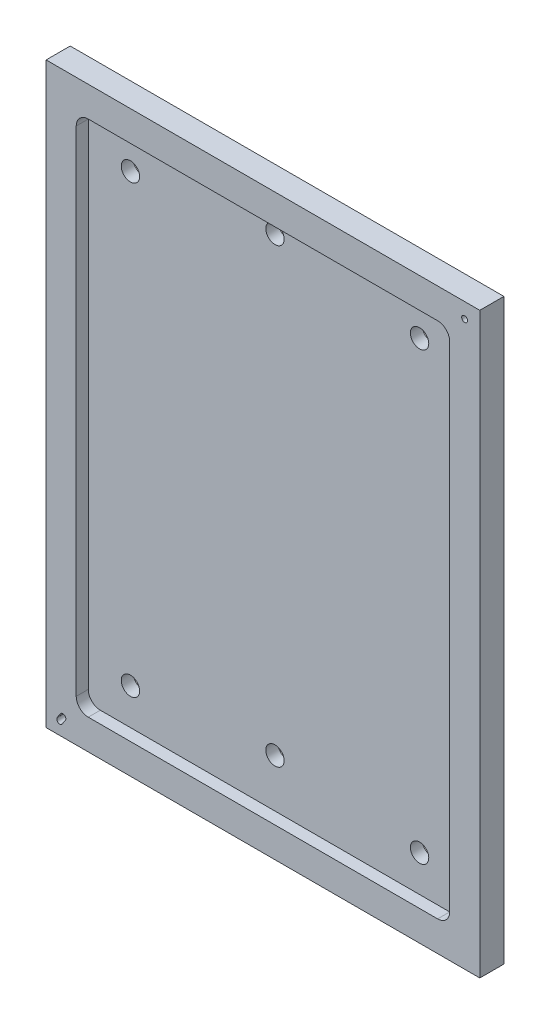
SolidWorks part; units mm, degrees
ref_plane "Front Plane" through (0, 0, 0) normal (0, 0, 1) x (1, 0, 0)
ref_plane "Top Plane" through (0, 0, 0) normal (0, 1, 0) x (1, 0, 0)
ref_plane "Right Plane" through (0, 0, 0) normal (1, 0, 0) x (0, 0, -1)
sketch "Sketch1" plane through (0, 0, 0) normal (0, 0, 1) x (1, 0, 0)
  line L1 (114.3, -152.4) -> (-114.3, -152.4)
  line L2 (114.3, -152.4) -> (114.3, 152.4)
  line L3 (114.3, 152.4) -> (-114.3, 152.4)
  line L4 (-114.3, -152.4) -> (-114.3, 152.4)
  line L5 (114.3, -152.4) -> (-114.3, 152.4) construction
  line L6 (114.3, 152.4) -> (-114.3, -152.4) construction
  point P0 (0, 0)
  dimension "D1" = 228.6
  dimension "D2" = 304.8
extrude "Boss-Extrude1" add sketch "Sketch1" along normal blind 12.7
sketch "Sketch2" plane through (0, 0, 12.7) normal (0, 0, 1) x (1, 0, 0)
  line L0 (-114.3, 152.4) -> (-114.3, -152.4) construction
  line L1 (92.075, -136.525) -> (-92.075, -136.525)
  line L2 (98.425, -130.175) -> (98.425, 130.175)
  line L3 (92.075, 136.525) -> (-92.075, 136.525)
  line L4 (-98.425, -130.175) -> (-98.425, 130.175)
  line L5 (98.425, -136.525) -> (-98.425, 136.525) construction
  line L6 (98.425, 136.525) -> (-98.425, -136.525) construction
  line L7 (114.3, 152.4) -> (-114.3, 152.4) construction
  arc A0 (-92.075, -136.525) -> (-98.425, -130.175) centre (-92.075, -130.175) cw
  arc A1 (92.075, -136.525) -> (98.425, -130.175) centre (92.075, -130.175) ccw
  arc A2 (98.425, 130.175) -> (92.075, 136.525) centre (92.075, 130.175) ccw
  arc A3 (-92.075, 136.525) -> (-98.425, 130.175) centre (-92.075, 130.175) ccw
  point P0 (0, 0)
  dimension "D3" = 6.35
  dimension "D1" = 15.875
  dimension "D2" = 15.875
extrude "Cut-Extrude1" cut sketch "Sketch2" against normal blind 6.35
sketch "Sketch4" plane through (0, 0, 6.35) normal (0, 0, 1) x (1, 0, 0)
  line L0 (114.3, 152.4) -> (-114.3, 152.4) construction
  line L4 (-114.3, 152.4) -> (-114.3, -152.4) construction
  line L5 (114.3, -152.4) -> (114.3, 152.4) construction
  line L6 (-114.3, -152.4) -> (114.3, -152.4) construction
  line L8 (-92.075, -136.525) -> (92.075, -136.525) construction
  circle A0 centre (-76.2, 117.4) radius 4.85
  circle A1 centre (76.2, 117.4) radius 4.85
  circle A2 centre (-76.2, -117.4) radius 4.85
  circle A3 centre (76.2, -117.4) radius 4.85
  circle A4 centre (0, 126.925) radius 4.85
  circle A5 centre (0, -111.125) radius 4.85
  dimension "D1" = 9.7
  dimension "D2" = 9.7
  dimension "D3" = 9.7
  dimension "D4" = 9.7
  dimension "D13" = 9.7
  dimension "D14" = 9.7
  dimension "D15" = 35
  dimension "D5" = 9.525
  dimension "D6" = 38.1
  dimension "D7" = 38.1
  dimension "D8" = 0
  dimension "D9" = 35
  dimension "D10" = 38.1
  dimension "D11" = 38.1
  dimension "D12" = 35
  dimension "D16" = 25.4
extrude "Cut-Extrude2" cut sketch "Sketch4" against normal through all
hole_wizard "Ø3.1 (3.1) Diameter Hole1" positions "Sketch5" profile "Sketch6" hole size "Ø3.1" standard "ANSI Metric"
sketch "Sketch5" plane through (0, 0, 12.7) normal (0, 0, 1) x (1, 0, 0)
  line L0 (114.3, 152.4) -> (-114.3, 152.4) construction
  line L1 (114.3, -152.4) -> (114.3, 152.4) construction
  point P0 (106.3, 144.4)
  dimension "D1" = 8
  dimension "D2" = 8
sketch "Sketch6" plane through (106.3, 144.4, 12.7) normal (1, 0, 0) x (0, -1, 0)
  line L0 (0, 0) -> (0, 5.9313)
  line L1 (0, 5.9313) -> (1.55, 5)
  line L2 (1.55, 5) -> (1.55, 0)
  line L5 (1.55, 0) -> (0, 0)
  line L10 (0, 5.9313) -> (-1.55, 5) construction
  line L11 (0, -6.35) -> (0, 107.95) construction
  dimension "Hole Dia." = 3.1
  dimension "Hole Depth" = 5
  dimension "Drill Angle" = 118
sketch "Sketch7" plane through (0, 0, 12.7) normal (0, 0, 1) x (1, 0, 0)
  line L0 (-107.1279, -145.6508) -> (-105.4721, -143.1492) construction
  line L1 (-108.4204, -144.7953) -> (-106.7646, -142.2937)
  line L2 (-105.8354, -146.5063) -> (-104.1796, -144.0047)
  line L3 (-114.3, -152.4) -> (114.3, -152.4) construction
  line L4 (-114.3, 152.4) -> (-114.3, -152.4) construction
  arc A0 (-108.4204, -144.7953) -> (-105.8354, -146.5063) centre (-107.1279, -145.6508) ccw
  arc A1 (-104.1796, -144.0047) -> (-106.7646, -142.2937) centre (-105.4721, -143.1492) ccw
  point P2 (-106.3, -144.4)
  point P7 (-107.5925, -143.5445)
  dimension "D1" = 3
  dimension "D2" = 3.1
  dimension "D3" = 8
  dimension "D4" = 8
  dimension "D5" = 56.5
extrude "Cut-Extrude3" cut sketch "Sketch7" against normal blind 5
hole_wizard "M4x0.7 Tapped Hole1" positions "Sketch8" profile "Sketch9" tap size "M4x0.7" standard "ANSI Metric"
sketch "Sketch8" plane through (0, 0, 0) normal (0, 0, -1) x (-1, 0, 0)
  line L0 (114.3, -152.4) -> (-114.3, -152.4) construction
  line L1 (-114.3, -152.4) -> (-114.3, 152.4) construction
  point P0 (-106.3, -102.4)
  point P2 (-106.3, 0)
  point P4 (-106.3, 113.6)
  point P14 (-114.3, 0)
  dimension "D1" = 266
  dimension "D2" = 8
  dimension "D3" = 50
cosmetic thread "Hole Thread1" parameters "D1"=3, "D2"=4
cosmetic thread "Hole Thread2" parameters "D1"=3, "D2"=4
cosmetic thread "Hole Thread3" parameters "D1"=3, "D2"=4
sketch "Sketch9" plane through (106.3, -102.4, 0) normal (1, 0, 0) x (0, 1, 0)
  line L0 (0, 0) -> (0, 6.3914)
  line L1 (0, 6.3914) -> (1.65, 5.4)
  line L2 (1.65, 5.4) -> (1.65, 0)
  line L5 (1.65, 0) -> (0, 0)
  line L10 (0, 6.3914) -> (-1.65, 5.4) construction
  line L11 (0, -6.35) -> (0, 107.95) construction
  dimension "Tap Drill Dia." = 3.3
  dimension "Tap Drill Depth" = 5.4
  dimension "Drill Angle" = 118
